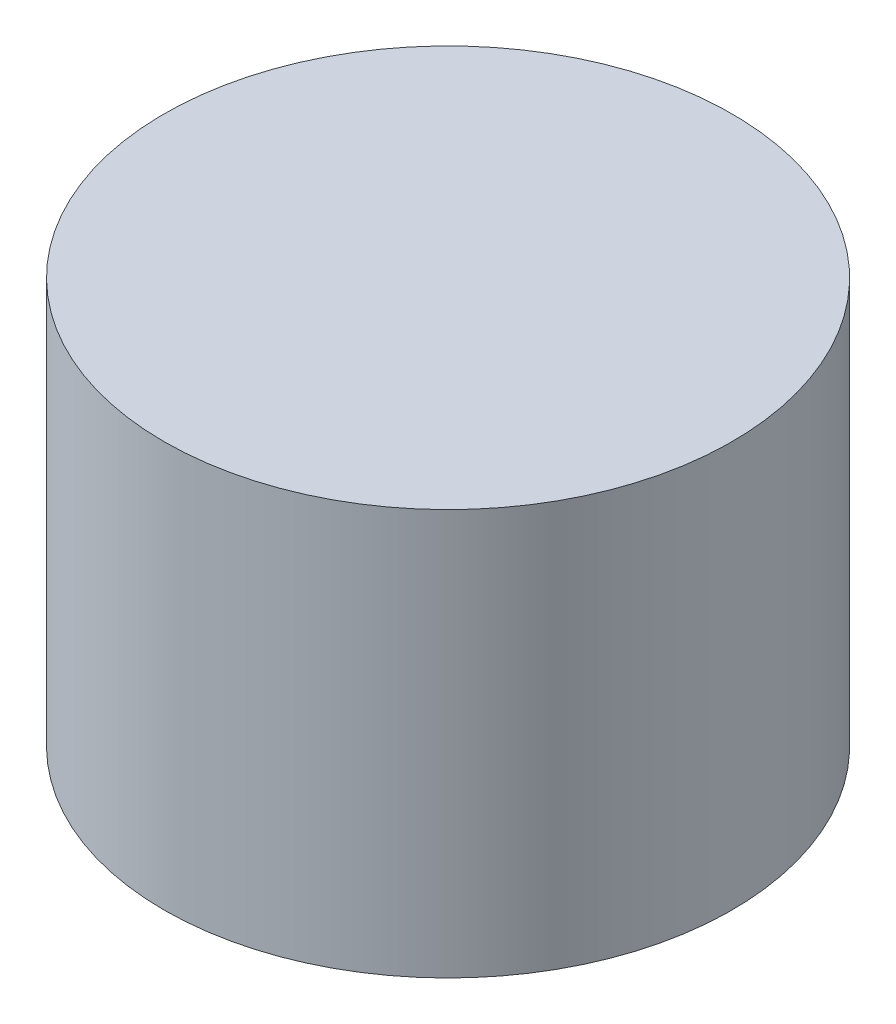
SolidWorks part; units mm, degrees
ref_plane "Front Plane" through (0, 0, 0) normal (0, 0, 1) x (1, 0, 0)
ref_plane "Top Plane" through (0, 0, 0) normal (0, 1, 0) x (1, 0, 0)
ref_plane "Right Plane" through (0, 0, 0) normal (1, 0, 0) x (0, 0, -1)
sketch "Sketch1" plane through (0, 0, 0) normal (0, 1, 0) x (1, 0, 0)
  circle A0 centre (0, 0) radius 14
  dimension "D1" = 28
extrude "Boss-Extrude1" add sketch "Sketch1" along normal blind 20
